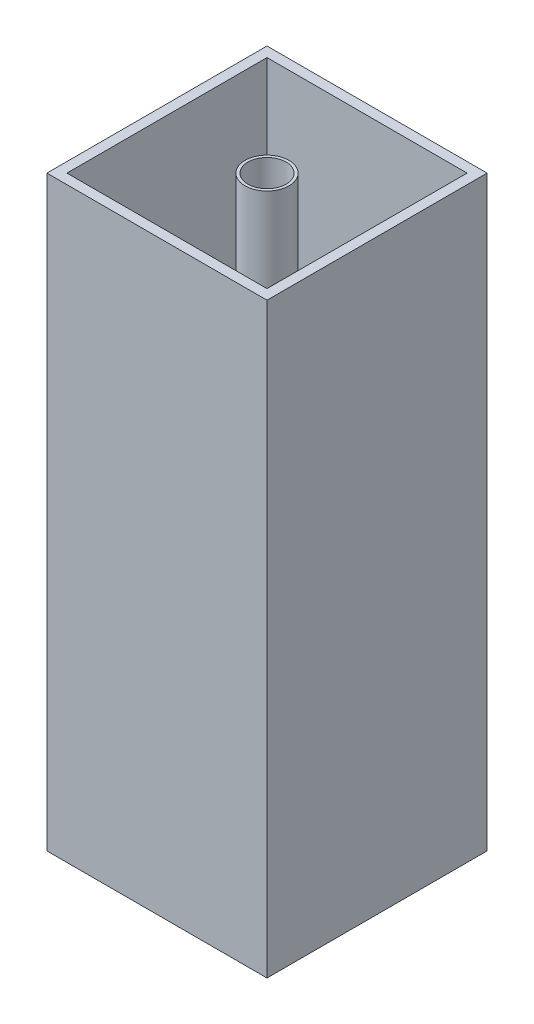
SolidWorks part; units mm, degrees
ref_plane "Front Plane" through (0, 0, 0) normal (0, 0, 1) x (1, 0, 0)
ref_plane "Top Plane" through (0, 0, 0) normal (0, 1, 0) x (1, 0, 0)
ref_plane "Right Plane" through (0, 0, 0) normal (1, 0, 0) x (0, 0, -1)
sketch "Sketch1" plane through (0, 0, 0) normal (0, 1, 0) x (1, 0, 0)
  circle A0 centre (0, 0) radius 15
  dimension "D1" = 30
extrude "Boss-Extrude1" add sketch "Sketch1" along normal blind 400
sketch "Sketch2" plane through (0, 400, 0) normal (0, 1, 0) x (1, 0, 0)
  circle A0 centre (0, 0) radius 13.0542
extrude "Cut-Extrude1" cut sketch "Sketch2" against normal blind 400
sketch "Sketch3" plane through (0, 400, 0) normal (0, 1, 0) x (1, 0, 0)
  line L1 (-75, -75) -> (75, -75)
  line L2 (-75, -75) -> (-75, 75)
  line L3 (-75, 75) -> (75, 75)
  line L4 (75, -75) -> (75, 75)
  line L5 (-75, -75) -> (75, 75) construction
  line L6 (-75, 75) -> (75, -75) construction
  line L7 (-68.1709, -68.1709) -> (68.1709, -68.1709)
  line L8 (-68.1709, -68.1709) -> (-68.1709, 68.1709)
  line L9 (-68.1709, 68.1709) -> (68.1709, 68.1709)
  line L10 (68.1709, -68.1709) -> (68.1709, 68.1709)
  line L11 (-68.1709, -68.1709) -> (68.1709, 68.1709) construction
  line L12 (-68.1709, 68.1709) -> (68.1709, -68.1709) construction
  circle A0 centre (0, 0) radius 15
  point P0 (0, 0)
  dimension "D1" = 150
  dimension "D2" = 150
extrude "Boss-Extrude2" add sketch "Sketch3" against normal blind 400 separate body contours L1 L4 L3 L2 L10 L7 L8 L9 region at (-72.8787, 400, 0)
sketch "Sketch4" plane through (0, 0, 0) normal (0, -1, 0) x (1, 0, 0)
  line L1 (-75, -75) -> (75, -75)
  line L2 (-75, -75) -> (-75, 75)
  line L3 (-75, 75) -> (75, 75)
  line L4 (75, -75) -> (75, 75)
  line L5 (-75, -75) -> (75, 75) construction
  line L6 (-75, 75) -> (75, -75) construction
  point P0 (0, 0)
extrude "Boss-Extrude3" add sketch "Sketch4" against normal blind 10
